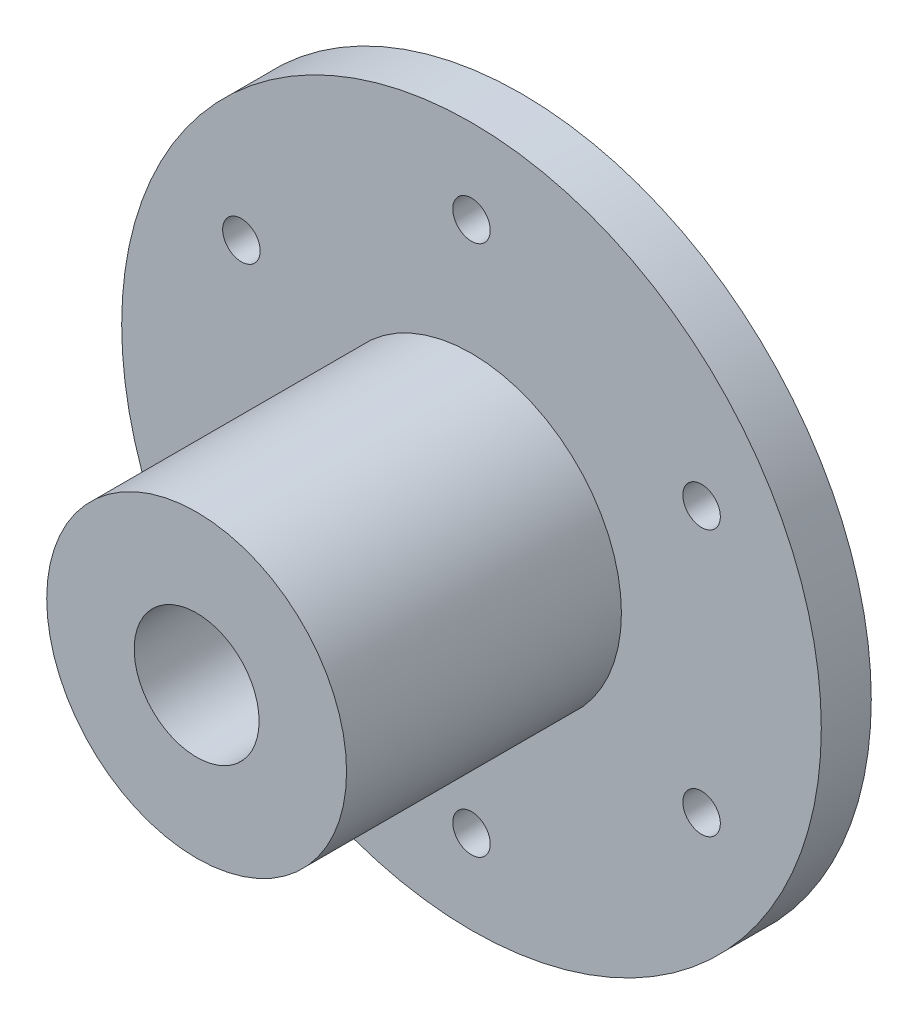
SolidWorks part; units mm, degrees
ref_plane "前视基准面" through (0, 0, 0) normal (0, 0, 1) x (1, 0, 0)
ref_plane "上视基准面" through (0, 0, 0) normal (0, 1, 0) x (1, 0, 0)
ref_plane "右视基准面" through (0, 0, 0) normal (1, 0, 0) x (0, 0, -1)
sketch "草图1" plane through (0, 0, 0) normal (0, 0, 1) x (1, 0, 0)
  circle A0 centre (0, 0) radius 28
  dimension "D1" = 56
extrude "凸台-拉伸1" add sketch "草图1" along normal blind 4 contours A0
sketch "草图2" plane through (0, 0, 4) normal (0, 0, 1) x (1, 0, 0)
  circle A0 centre (0, 0) radius 12
  dimension "D1" = 24
extrude "凸台-拉伸2" add sketch "草图2" along normal blind 22 contours A0
sketch "草图3" plane through (0, 0, 26) normal (0, 0, 1) x (1, 0, 0)
  circle A0 centre (0, 0) radius 5
  dimension "D1" = 10
extrude "切除-拉伸1" cut sketch "草图3" against normal blind 60 contours A0
sketch "草图4" plane through (0, 0, 0) normal (0, 0, -1) x (-1, 0, 0)
  circle A0 centre (0, 21.2656) radius 1.5
  dimension "D1" = 3
extrude "切除-拉伸2" cut sketch "草图4" against normal blind 7 contours A0
ref_axis "基准轴1" through (0, 0, -1.3) along (0, 0, 1)
pattern_circular "阵列(圆周)1" count 6 every 60 about axis through (0, 0, -1.3) along (0, 0, 1) of "切除-拉伸2"
sketch "草图5" plane through (0, 0, 0) normal (0, 1, 0) x (1, 0, 0)
  line L0 (0, 1.3) -> (0, -27.3) construction
  circle A0 centre (0, -16.2233) radius 1.5
  dimension "D1" = 3
extrude "切除-拉伸3" cut sketch "草图5" against normal blind 15 contours A0
